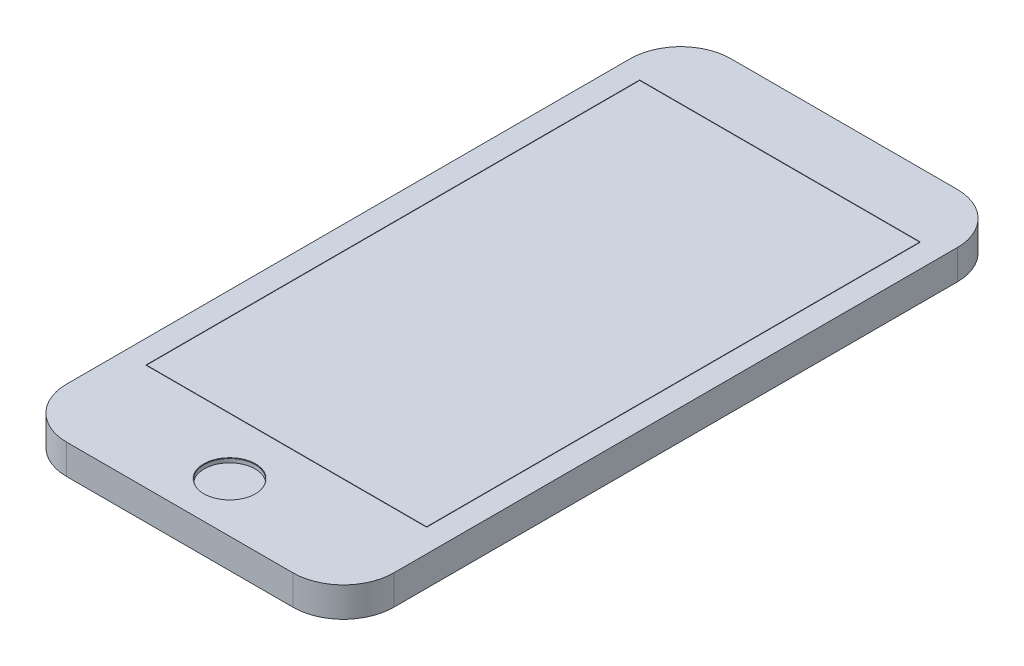
SolidWorks part; units mm, degrees
ref_plane "Спереди" through (0, 0, 0) normal (0, 0, 1) x (1, 0, 0)
ref_plane "Сверху" through (0, 0, 0) normal (0, 1, 0) x (1, 0, 0)
ref_plane "Справа" through (0, 0, 0) normal (1, 0, 0) x (0, 0, -1)
sketch "Эскиз1" plane through (0, 0, 0) normal (0, 1, 0) x (1, 0, 0)
  line L1 (26.95, 79.1) -> (-26.95, 79.1)
  line L2 (38.95, 67.1) -> (38.95, -67.1)
  line L3 (26.95, -79.1) -> (-26.95, -79.1)
  line L4 (-38.95, 67.1) -> (-38.95, -67.1)
  line L5 (38.95, 79.1) -> (-38.95, -79.1) construction
  line L6 (38.95, -79.1) -> (-38.95, 79.1) construction
  arc A0 (26.95, -79.1) -> (38.95, -67.1) centre (26.95, -67.1) ccw
  arc A1 (38.95, 67.1) -> (26.95, 79.1) centre (26.95, 67.1) ccw
  arc A2 (-26.95, -79.1) -> (-38.95, -67.1) centre (-26.95, -67.1) cw
  arc A3 (-38.95, 67.1) -> (-26.95, 79.1) centre (-26.95, 67.1) cw
  point P0 (0, 0)
  dimension "D3" = 12
  dimension "D1" = 77.9
  dimension "D2" = 158.2
extrude "Бобышка-Вытянуть1" add sketch "Эскиз1" along normal blind 7.1
sketch "Эскиз2" plane through (0, 7.1, 0) normal (0, 1, 0) x (1, 0, 0)
  line L0 (0, 79.1) -> (0, -79.1) construction
  line L1 (26.95, 79.1) -> (-26.95, 79.1) construction
  line L2 (-26.95, -79.1) -> (26.95, -79.1) construction
  line L4 (-33.3428, 63.7498) -> (33.3428, 63.7498)
  line L5 (-33.3428, 63.7498) -> (-33.3428, -53.684)
  line L6 (-33.3428, -53.684) -> (33.3428, -53.684)
  line L7 (33.3428, 63.7498) -> (33.3428, -53.684)
  line L8 (-33.3428, 63.7498) -> (33.3428, -53.684) construction
  line L9 (-33.3428, -53.684) -> (33.3428, 63.7498) construction
  circle A0 centre (0, -67.2515) radius 6.0708
  point P8 (0, 5.0329)
  point P13 (0, 0)
extrude "Вырез-Вытянуть1" cut sketch "Эскиз2" against normal blind 1 contours A0 region at (0, 7.1, 67.2515)
extrude "Вырез-Вытянуть-Тонкостенный1" cut sketch "Эскиз2<4>" against normal blind 0.1 thin thin type one direction wall 0.1
sketch "Эскиз2<4>" plane through (0, 7.1, 0) normal (0, 1, 0) x (1, 0, 0) same geometry as "Эскиз2"
